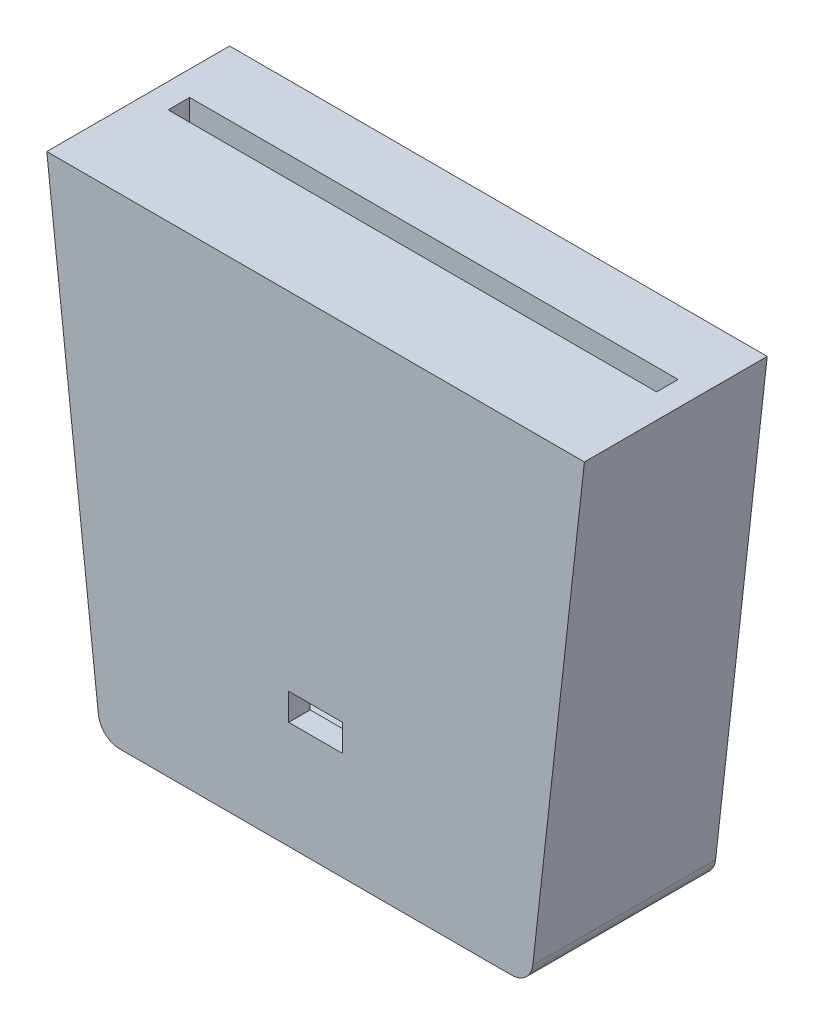
SolidWorks part; units mm, degrees
ref_plane "Front Plane" through (0, 0, 0) normal (0, 0, 1) x (1, 0, 0)
ref_plane "Top Plane" through (0, 0, 0) normal (0, 1, 0) x (1, 0, 0)
ref_plane "Right Plane" through (0, 0, 0) normal (1, 0, 0) x (0, 0, -1)
sketch "Sketch1" plane through (0, 0, 0) normal (0, 0, 1) x (1, 0, 0)
  line L0 (0, 56.7961) -> (0, -56.7961) construction
  line L1 (63.5, 56.7961) -> (-63.5, 56.7961)
  line L2 (-63.5, 56.7961) -> (-51.3049, -52.2806)
  line L3 (-46.2563, -56.7961) -> (46.2563, -56.7961)
  line L4 (63.5, 56.7961) -> (51.3049, -52.2806)
  line L5 (6.35, -25.0461) -> (-6.35, -25.0461)
  line L6 (-6.35, -25.0461) -> (-6.35, -31.3961)
  line L7 (-6.35, -31.3961) -> (6.35, -31.3961)
  line L8 (6.35, -25.0461) -> (6.35, -31.3961)
  arc A0 (-51.3049, -52.2806) -> (-46.2563, -56.7961) centre (-46.2563, -51.7161) ccw
  arc A1 (51.3049, -52.2806) -> (46.2563, -56.7961) centre (46.2563, -51.7161) cw
  point P10 (-50.8, -56.7961)
  point P16 (0, -31.3961)
  point P18 (0, -25.0461)
  dimension "D4" = 5.08
  dimension "D6" = 6.35
  dimension "D7" = 6.35
  dimension "D8" = 25.4
  dimension "D1" = 50.8
  dimension "D2" = 63.5
  dimension "D3" = 56.7961
  dimension "D5" = 109.0767
extrude "Boss-Extrude1" add sketch "Sketch1" against normal blind 5.08
sketch "Sketch2" plane through (0, 0, -5.08) normal (0, 0, 1) x (1, 0, 0)
  line L0 (0, 56.7961) -> (0, -56.7961) construction
  line L1 (63.5, 56.7961) -> (-63.5, 56.7961)
  line L2 (-63.5, 56.7961) -> (-51.3049, -52.2806)
  line L3 (-46.2563, -56.7961) -> (46.2563, -56.7961)
  line L4 (63.5, 56.7961) -> (51.3049, -52.2806)
  line L5 (6.35, -25.0461) -> (-6.35, -25.0461)
  line L6 (-6.35, -25.0461) -> (-6.35, -31.3961)
  line L7 (-6.35, -31.3961) -> (6.35, -31.3961)
  line L8 (6.35, -25.0461) -> (6.35, -31.3961)
  line L9 (-6.35, -25.0461) -> (-6.35, -31.3961) construction
  line L10 (6.35, -25.0461) -> (-6.35, -25.0461) construction
  line L11 (-57.8204, 51.7161) -> (57.8204, 51.7161)
  line L12 (57.8204, 51.7161) -> (46.7612, -47.2006)
  line L13 (41.7126, -51.7161) -> (-41.7126, -51.7161)
  line L14 (-57.8204, 51.7161) -> (-46.7612, -47.2006)
  arc A0 (-51.3049, -52.2806) -> (-46.2563, -56.7961) centre (-46.2563, -51.7161) ccw
  arc A1 (51.3049, -52.2806) -> (46.2563, -56.7961) centre (46.2563, -51.7161) cw
  arc A2 (46.7612, -47.2006) -> (41.7126, -51.7161) centre (41.7126, -46.6361) cw
  arc A3 (-46.7612, -47.2006) -> (-41.7126, -51.7161) centre (-41.7126, -46.6361) ccw
  point P10 (-50.8, -56.7961)
  point P16 (0, -31.3961)
  point P18 (0, -25.0461)
  point P30 (0, -51.7161)
  point P33 (0, 51.7161)
  arc M18 (51.3049, -52.2806) -> (46.2563, -56.7961) centre (46.2563, -51.7161) cw
  line M19 (46.2563, -56.7961) -> (-46.2563, -56.7961)
  arc M20 (-46.2563, -56.7961) -> (-51.3049, -52.2806) centre (-46.2563, -51.7161) cw
  line M21 (-51.3049, -52.2806) -> (-63.5, 56.7961)
  line M22 (-63.5, 56.7961) -> (63.5, 56.7961)
  line M23 (63.5, 56.7961) -> (51.3049, -52.2806)
  dimension "D4" = 5.08
  dimension "D6" = 6.35
  dimension "D7" = 6.35
  dimension "D8" = 25.4
  dimension "D9" = 0
  dimension "D10" = 5.08
  dimension "D1" = 50.8
  dimension "D2" = 63.5
  dimension "D3" = 5.08
  dimension "D5" = 109.0767
extrude "Boss-Extrude2" add sketch "Sketch2" against normal blind 38.1 contours L0 L1 L13 A2 L12 L11 M23 M18 M19 | L0 L11 L14 A3 L13 L3 M22 M20 M21 region at (31.75, 55.4948, -5.08) region at (-1.3014, 54.2561, -5.08)
sketch "Sketch4" plane through (0, 56.7961, -56.7961) normal (0, -1, 0) x (1, 0, 0)
  line L0 (57.6928, 28.8561) -> (57.6928, 33.9361)
  line L1 (57.6928, 28.8561) -> (-57.6928, 28.8561)
  line L2 (57.6928, 33.9361) -> (-57.6928, 33.9361)
  line L3 (-57.6928, 28.8561) -> (-57.6928, 33.9361)
  line L4 (63.5, 56.7961) -> (-63.5, 56.7961) construction
  dimension "D1" = 115.3856
  dimension "D2" = 22.86
  dimension "D4" = 5.08
extrude "Cut-Extrude1" cut sketch "Sketch4" along normal blind 5.08
sketch "Sketch6" plane through (0, 0, -43.18) normal (0, 0, 1) x (1, 0, 0)
  line L0 (0, 50.5747) -> (0, -51.7161) construction
  line L3 (-52.9958, 8.564) -> (-33.9458, 8.564)
  line L5 (-33.9458, 8.564) -> (-33.9458, -4.136)
  line L6 (-33.9458, -4.136) -> (-51.5759, -4.136)
  line L8 (33.9458, -4.136) -> (51.5759, -4.136)
  line L9 (33.9458, 8.564) -> (33.9458, -4.136)
  line L10 (52.9958, 8.564) -> (33.9458, 8.564)
  line L11 (-51.5759, -4.136) -> (-52.9958, 8.564)
  line L12 (52.9958, 8.564) -> (51.5759, -4.136)
  line L13 (-57.8204, 51.7161) -> (57.8204, 51.7161) construction
  dimension "D1" = 19.05
  dimension "D2" = 12.7
  dimension "D3" = 33.9458
  dimension "D4" = 4.8246
  dimension "D5" = 6.2445
  dimension "D6" = 43.1521
extrude "Boss-Extrude3" add sketch "Sketch6" along normal blind 2.54
sketch "Sketch7" plane through (0, 0, -43.18) normal (0, 0, 1) x (1, 0, 0)
  line L0 (-43.4708, 8.564) -> (-42.7609, -4.136) construction
  line L1 (-63.5, 56.7961) -> (63.5, 56.7961) construction
  line L2 (-51.5759, -4.136) -> (-33.9458, -4.136) construction
  line L3 (0, 56.7961) -> (0, -51.7161) construction
  line L4 (-33.9458, 8.564) -> (-52.9958, 8.564) construction
  line L6 (-33.9458, -4.136) -> (-33.9458, 8.564) construction
  line L7 (-57.8204, 51.7161) -> (57.8204, 51.7161) construction
  circle A0 centre (-43.1159, 2.214) radius 1.905
  circle A2 centre (43.1159, 2.214) radius 1.905
  dimension "D1" = 3.81
extrude "Cut-Extrude2" cut sketch "Sketch7" along normal blind 2.54
sketch "Sketch8" plane through (0, 0, -5.08) normal (0, 0, -1) x (-1, 0, 0)
  line L0 (0, 51.7161) -> (0, -51.7161) construction
  line L1 (57.8204, 51.7161) -> (-57.8204, 51.7161) construction
  line L2 (-41.7126, -51.7161) -> (41.7126, -51.7161) construction
  line L3 (25.085, 41.5561) -> (-25.085, 41.5561)
  line L4 (-25.085, 41.5561) -> (-25.085, -20.9787)
  line L5 (-25.085, -20.9787) -> (25.085, -20.9787)
  line L6 (25.085, 41.5561) -> (25.085, -20.9787)
  point P11 (0, -20.9787)
  point P12 (0, 41.5561)
  dimension "D1" = 25.085
  dimension "D2" = 62.5348
  dimension "D3" = 10.16
extrude "Boss-Extrude4" add sketch "Sketch8" along normal blind 9.017
sketch "Sketch9" plane through (0, 41.5561, 0) normal (0, 1, 0) x (1, 0, 0)
  line L0 (22.545, 5.08) -> (-22.545, 5.08)
  line L1 (22.545, 5.08) -> (22.545, 11.557)
  line L2 (-22.545, 5.08) -> (-22.545, 11.557)
  line L3 (22.545, 11.557) -> (-22.545, 11.557)
  line L4 (-25.085, 5.08) -> (25.085, 5.08) construction
  line L5 (25.085, 14.097) -> (25.085, 5.08) construction
  line L6 (-25.085, 14.097) -> (-25.085, 5.08) construction
  line L7 (-25.085, 14.097) -> (25.085, 14.097) construction
  dimension "D1" = 2.54
  dimension "D2" = 2.54
  dimension "D3" = 2.54
extrude "Cut-Extrude3" cut sketch "Sketch9" against normal blind 61.3918
